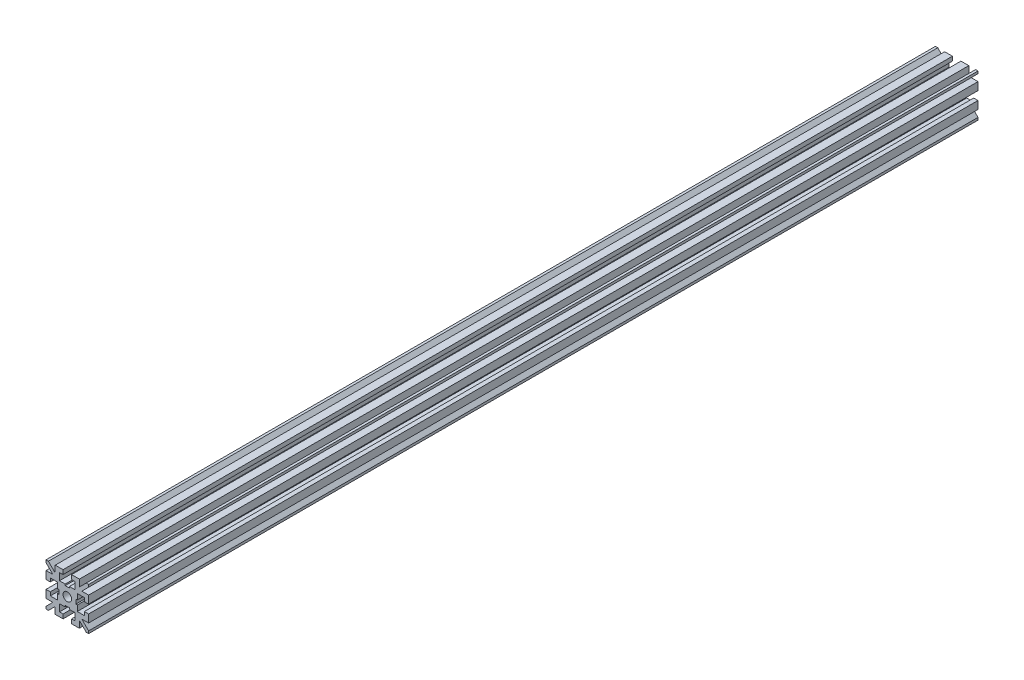
SolidWorks part; units mm, degrees
ref_plane "Front Plane" through (0, 0, 0) normal (0, 0, 1) x (1, 0, 0)
ref_plane "Top Plane" through (0, 0, 0) normal (0, 1, 0) x (1, 0, 0)
ref_plane "Right Plane" through (0, 0, 0) normal (1, 0, 0) x (0, 0, -1)
sketch "Sketch1" plane through (0, 0, 0) normal (0, 0, 1) x (1, 0, 0)
  line L1 (-9.0006, 3.7616) -> (5.9994, 3.7616)
  line L2 (-9.0006, 3.7616) -> (-9.0006, -11.2384)
  line L3 (-9.0006, -11.2384) -> (5.9994, -11.2384)
  line L4 (5.9994, 3.7616) -> (5.9994, -11.2384)
  dimension "D1" = 15
  dimension "D2" = 15
extrude "Boss-Extrude1" add sketch "Sketch1" along normal blind 313
sketch "Sketch2" plane through (0, 0, 313) normal (0, 0, 1) x (1, 0, 0)
  line L0 (-9.0006, 3.7616) -> (5.9994, -11.2384) construction
  line L1 (5.9994, 3.7616) -> (-9.0006, -11.2384) construction
  line L4 (1.9994, -4.4884) -> (1.9994, -6.4884)
  line L5 (5.9994, -3.7384) -> (1.9994, -3.7384) construction
  line L6 (5.9994, -11.2384) -> (5.9994, 3.7616) construction
  line L7 (-1.5006, 3.7616) -> (-1.5006, -3.7384) construction
  line L8 (5.9994, 3.7616) -> (-9.0006, 3.7616) construction
  line L9 (-9.0006, -3.7384) -> (-1.5006, -3.7384) construction
  line L10 (-9.0006, 3.7616) -> (-9.0006, -11.2384) construction
  line L11 (-1.5006, -11.2384) -> (-1.5006, -3.7384) construction
  line L12 (-9.0006, -11.2384) -> (5.9994, -11.2384) construction
  line L13 (1.9994, -4.4884) -> (1.4994, -4.4884)
  line L14 (1.9994, -0.9884) -> (4.4994, -0.9884)
  line L15 (1.9994, -0.9884) -> (1.9994, -2.9884)
  line L16 (1.9994, -6.4884) -> (4.4994, -6.4884)
  line L17 (4.4994, -0.9884) -> (4.4994, -6.4884)
  line L18 (-4.2506, -7.2384) -> (-4.2506, -9.7384)
  line L19 (1.9994, -2.9884) -> (1.4994, -2.9884)
  line L20 (1.4994, -4.4884) -> (1.4994, -2.9884)
  line L21 (1.4994, -3.7384) -> (-0.0006, -3.7384) construction
  line L22 (-2.2506, -7.2384) -> (-4.2506, -7.2384)
  line L23 (-2.2506, -7.2384) -> (-2.2506, -6.7384)
  line L24 (-2.2506, -6.7384) -> (-0.7506, -6.7384)
  line L25 (-0.7506, -7.2384) -> (-0.7506, -6.7384)
  line L26 (1.2494, -7.2384) -> (-0.7506, -7.2384)
  line L27 (1.2494, -7.2384) -> (1.2494, -9.7384)
  line L28 (1.2494, -9.7384) -> (-4.2506, -9.7384)
  line L29 (-5.0006, -0.9884) -> (-7.5006, -0.9884)
  line L30 (-5.0006, -2.9884) -> (-5.0006, -0.9884)
  line L31 (-5.0006, -2.9884) -> (-4.5006, -2.9884)
  line L32 (-4.5006, -2.9884) -> (-4.5006, -4.4884)
  line L33 (-5.0006, -4.4884) -> (-4.5006, -4.4884)
  line L34 (-5.0006, -6.4884) -> (-5.0006, -4.4884)
  line L35 (-5.0006, -6.4884) -> (-7.5006, -6.4884)
  line L36 (-7.5006, -6.4884) -> (-7.5006, -0.9884)
  line L37 (1.2494, -0.2384) -> (1.2494, 2.2616)
  line L38 (-0.7506, -0.2384) -> (1.2494, -0.2384)
  line L39 (-0.7506, -0.2384) -> (-0.7506, -0.7384)
  line L40 (-0.7506, -0.7384) -> (-2.2506, -0.7384)
  line L41 (-2.2506, -0.2384) -> (-2.2506, -0.7384)
  line L42 (-4.2506, -0.2384) -> (-2.2506, -0.2384)
  line L43 (-4.2506, -0.2384) -> (-4.2506, 2.2616)
  line L44 (-4.2506, 2.2616) -> (1.2494, 2.2616)
  circle A0 centre (-1.5006, -3.7384) radius 1.5
  point P60 (-1.5006, -3.7384)
  dimension "D1" = 5.5
  dimension "D2" = 2.5
  dimension "D3" = 1.5
  dimension "D4" = 2.75
  dimension "D5" = 0.5
  dimension "D6" = 1.5
  dimension "D7" = 0.75
  dimension "D8" = 4
extrude "Cut-Extrude1" cut sketch "Sketch2" against normal up to surface (313 mm away) up to face at (-1.5006, -3.7384, 0)
sketch "Sketch3" plane through (0, 0, 313) normal (0, 0, 1) x (1, 0, 0)
  line L0 (5.9994, 3.7616) -> (-9.0006, -11.2384) construction
  line L1 (-9.0006, 3.7616) -> (5.9994, -11.2384) construction
  line L2 (5.1509, 3.7616) -> (2.7494, 1.3602)
  line L3 (5.9994, 3.7616) -> (-9.0006, 3.7616) construction
  line L4 (2.7494, 1.3602) -> (2.7494, 3.7616)
  line L5 (2.7494, 3.7616) -> (5.1509, 3.7616)
  line L6 (1.2494, -0.2384) -> (1.2494, 2.2616) construction
  line L7 (5.9994, 0.5116) -> (5.9994, 2.9131)
  line L8 (3.5979, 0.5116) -> (5.9994, 0.5116)
  line L9 (5.9994, 2.9131) -> (3.5979, 0.5116)
  line L10 (1.2494, 2.2616) -> (-4.2506, 2.2616) construction
  line L11 (-3.0006, 3.7616) -> (-0.0006, 3.7616)
  line L12 (-3.0006, 3.7616) -> (-3.0006, 2.2616)
  line L13 (-3.0006, 2.2616) -> (-0.0006, 2.2616)
  line L14 (-0.0006, 3.7616) -> (-0.0006, 2.2616)
  line L15 (-2.2506, -0.7384) -> (-0.7506, -0.7384) construction
  line L16 (2.7494, -8.8369) -> (2.7494, -11.2384)
  line L17 (2.7494, -11.2384) -> (5.1509, -11.2384)
  line L18 (5.1509, -11.2384) -> (2.7494, -8.8369)
  line L19 (5.9994, -10.3898) -> (3.5979, -7.9884)
  line L20 (3.5979, -7.9884) -> (5.9994, -7.9884)
  line L21 (5.9994, -7.9884) -> (5.9994, -10.3898)
  line L22 (5.9994, -5.2384) -> (4.4994, -5.2384)
  line L23 (5.9994, -2.2384) -> (5.9994, -5.2384)
  line L24 (5.9994, -2.2384) -> (4.4994, -2.2384)
  line L25 (4.4994, -2.2384) -> (4.4994, -5.2384)
  line L26 (-6.5991, -7.9884) -> (-9.0006, -7.9884)
  line L27 (-9.0006, -7.9884) -> (-9.0006, -10.3898)
  line L28 (-9.0006, -10.3898) -> (-6.5991, -7.9884)
  line L29 (-8.1521, -11.2384) -> (-5.7506, -8.8369)
  line L30 (-5.7506, -8.8369) -> (-5.7506, -11.2384)
  line L31 (-5.7506, -11.2384) -> (-8.1521, -11.2384)
  line L32 (-3.0006, -11.2384) -> (-3.0006, -9.7384)
  line L33 (-0.0006, -11.2384) -> (-3.0006, -11.2384)
  line L34 (-0.0006, -11.2384) -> (-0.0006, -9.7384)
  line L35 (-0.0006, -9.7384) -> (-3.0006, -9.7384)
  line L36 (-5.7506, 1.3602) -> (-5.7506, 3.7616)
  line L37 (-5.7506, 3.7616) -> (-8.1521, 3.7616)
  line L38 (-8.1521, 3.7616) -> (-5.7506, 1.3602)
  line L39 (-9.0006, 2.9131) -> (-6.5991, 0.5116)
  line L40 (-6.5991, 0.5116) -> (-9.0006, 0.5116)
  line L41 (-9.0006, 0.5116) -> (-9.0006, 2.9131)
  line L42 (-9.0006, -2.2384) -> (-7.5006, -2.2384)
  line L43 (-9.0006, -5.2384) -> (-9.0006, -2.2384)
  line L44 (-9.0006, -5.2384) -> (-7.5006, -5.2384)
  line L45 (-7.5006, -5.2384) -> (-7.5006, -2.2384)
  point P24 (-1.5006, -0.7384)
  point P27 (-1.5006, -3.7384)
  point P61 (-1.5006, -3.7384)
  dimension "D1" = 0.6
  dimension "D2" = 1.5
  dimension "D3" = 3
  dimension "D4" = 1.5
  dimension "D5" = 4
extrude "Cut-Extrude2" cut sketch "Sketch3" against normal up to surface (313 mm away) up to face at (-1.5006, 0.2616, 0)
